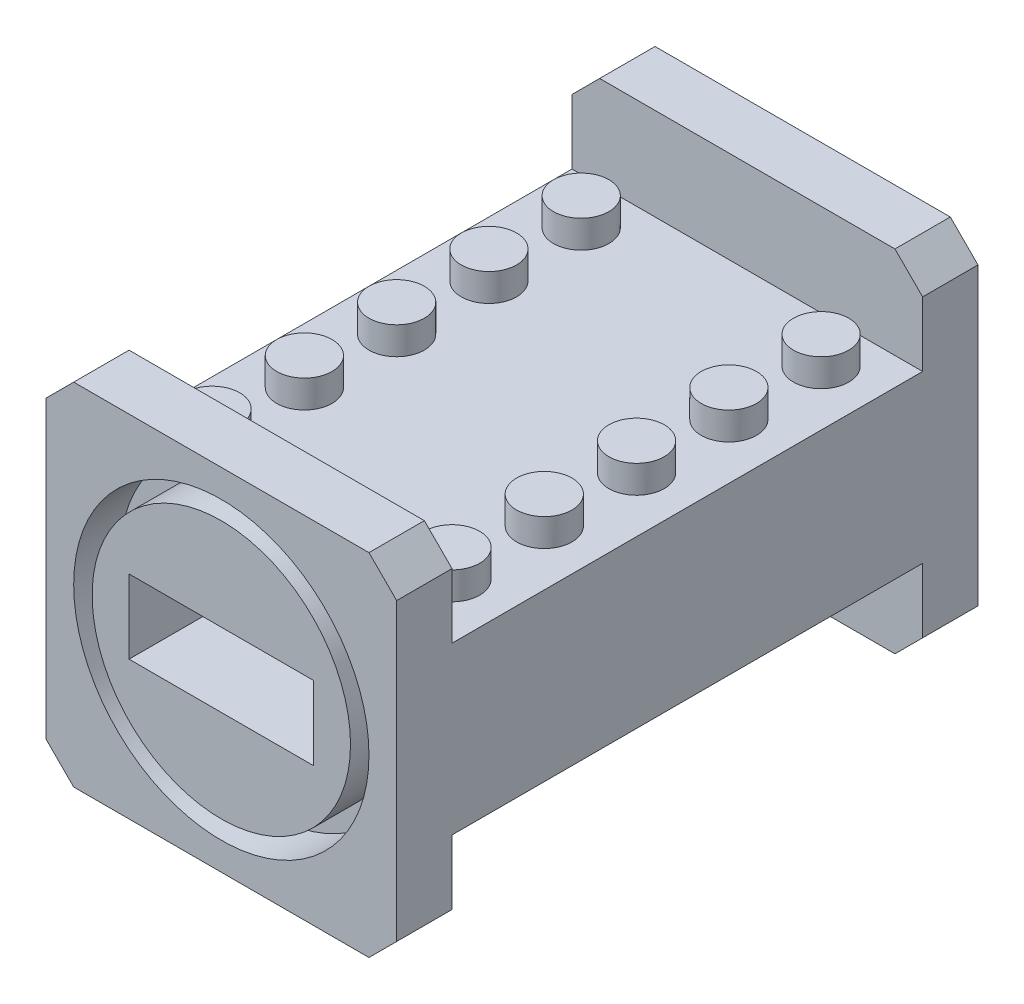
SolidWorks part; units mm, degrees
ref_plane "Front Plane" through (0, 0, 0) normal (0, 0, 1) x (1, 0, 0)
ref_plane "Top Plane" through (0, 0, 0) normal (0, 1, 0) x (1, 0, 0)
ref_plane "Right Plane" through (0, 0, 0) normal (1, 0, 0) x (0, 0, -1)
sketch "Sketch2" plane through (0, 0, 0) normal (0, 0, 1) x (1, 0, 0)
  line L1 (0, 0) -> (38, 0)
  line L2 (0, 0) -> (0, 38)
  line L3 (0, 38) -> (38, 38)
  line L4 (38, 0) -> (38, 38)
  dimension "D1" = 38
  dimension "D2" = 38
extrude "Boss-Extrude1" add sketch "Sketch2" against normal blind 63
sketch "Sketch3" plane through (38, 0, 0) normal (1, 0, 0) x (0, 0, -1)
  line L0 (0, 38) -> (6, 38) construction
  line L1 (63, 38) -> (0, 38) construction
  line L2 (63, 38) -> (57, 38) construction
  line L3 (0, 0) -> (6, 0) construction
  line L4 (63, 0) -> (0, 0) construction
  line L5 (63, 0) -> (57, 0) construction
  line L6 (6, 38) -> (6, 28)
  line L7 (6, 0) -> (6, 10)
  line L8 (57, 38) -> (57, 28)
  line L9 (57, 28) -> (6, 28)
  line L10 (6, 38) -> (57, 38)
  line L11 (6, 10) -> (57, 10)
  line L12 (57, 10) -> (57, 0)
  line L13 (57, 0) -> (6, 0)
  dimension "D1" = 6
  dimension "D2" = 10
extrude "Cut-Extrude1" cut sketch "Sketch3" against normal through all
sketch "Sketch4" plane through (0, 0, 0) normal (0, 0, 1) x (1, 0, 0)
  line L0 (0, 19) -> (38, 19) construction
  line L1 (0, 38) -> (0, 0) construction
  line L2 (38, 0) -> (38, 38) construction
  line L4 (9, 15) -> (29, 15)
  line L5 (9, 15) -> (9, 23)
  line L6 (9, 23) -> (29, 23)
  line L7 (29, 15) -> (29, 23)
  line L8 (9, 15) -> (29, 23) construction
  line L9 (9, 23) -> (29, 15) construction
  point P6 (19, 19)
  dimension "D1" = 8
  dimension "D2" = 20
extrude "Cut-Extrude2" cut sketch "Sketch4" against normal through all
sketch "Sketch5" plane through (0, 0, 0) normal (0, 0, 1) x (1, 0, 0)
  line L0 (0, 19) -> (38, 19) construction
  line L1 (0, 38) -> (0, 0) construction
  line L2 (38, 0) -> (38, 38) construction
  circle A0 centre (19, 19) radius 14
  circle A1 centre (19, 19) radius 16
  dimension "D1" = 28
  dimension "D2" = 2
extrude "Cut-Extrude3" cut sketch "Sketch5" against normal blind 5
sketch "Sketch6" plane through (0, 28, 0) normal (0, 1, 0) x (1, 0, 0)
  line L0 (19, 57) -> (19, 6) construction
  line L1 (0, 57) -> (38, 57) construction
  line L2 (0, 6) -> (38, 6) construction
  line L3 (32, 12) -> (38, 12) construction
  line L4 (38, 6) -> (38, 57) construction
  line L5 (32, 12) -> (32, 6) construction
  line L6 (0, 6) -> (38, 6) construction
  circle A0 centre (32, 12) radius 3
  circle A1 centre (32, 22) radius 3
  circle A2 centre (32, 32) radius 3
  circle A3 centre (32, 42) radius 3
  circle A4 centre (32, 52) radius 3
  circle A5 centre (6, 12) radius 3
  circle A6 centre (6, 22) radius 3
  circle A7 centre (6, 32) radius 3
  circle A8 centre (6, 42) radius 3
  circle A9 centre (6, 52) radius 3
  dimension "D1" = 6
  dimension "D2" = 6
  dimension "D4" = 10
  dimension "D3" = 5
extrude "Boss-Extrude2" add sketch "Sketch6" along normal blind 3
extrude "Boss-Extrude3" add sketch "Sketch6<2>" against normal blind 3 from surface starting at face at (19, 10, -31.5)
sketch "Sketch6<2>" plane through (0, 28, 0) normal (0, 1, 0) x (1, 0, 0) same geometry as "Sketch6"
chamfer "Chamfer1" distance 3 angle 45 8 edges at (38, 0, -60) (38, 38, -60) (0, 38, -60) (0, 0, -60) (0, 0, -3) (38, 0, -3) (0, 38, -3) (38, 38, -3)
